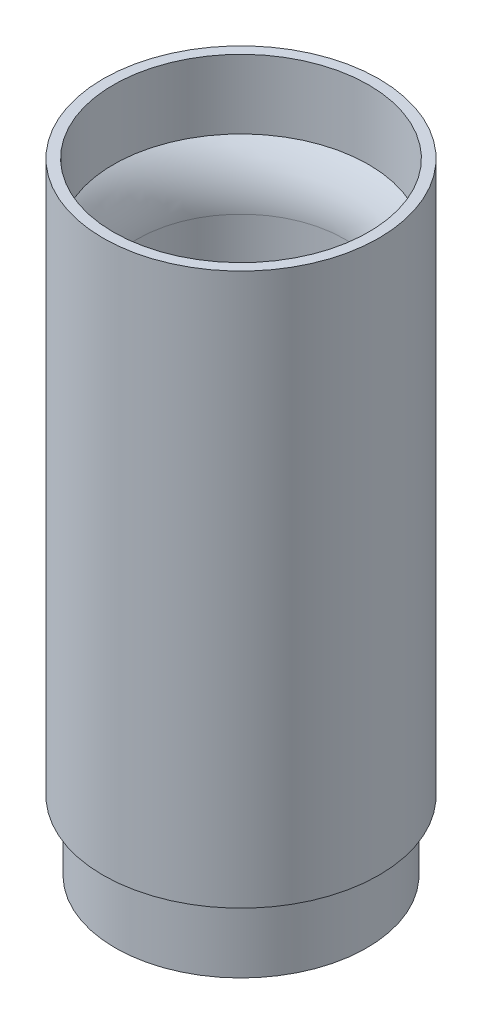
SolidWorks part; units mm, degrees
material "自定义塑料"
ref_plane "前视基准面" through (0, 0, 0) normal (0, 0, 1) x (1, 0, 0)
ref_plane "上视基准面" through (0, 0, 0) normal (0, 1, 0) x (1, 0, 0)
ref_plane "右视基准面" through (0, 0, 0) normal (1, 0, 0) x (0, 0, -1)
sketch "草图1" plane through (0, 0, 0) normal (0, 1, 0) x (1, 0, 0)
  circle A0 centre (0, 0) radius 18.25
  dimension "D1" = 36.5
extrude "凸台-拉伸1" add sketch "草图1" along normal blind 10
sketch "草图3" plane through (0, 0, 0) normal (0, -1, 0) x (1, 0, 0)
  circle A0 centre (0, 0) radius 15
extrude "切除-拉伸1" cut sketch "草图3" against normal blind 8
sketch "草图4" plane through (0, 10, 0) normal (0, 1, 0) x (1, 0, 0)
  circle A1 centre (0, 0) radius 20
  circle A2 centre (0, 0) radius 15
extrude "凸台-拉伸2" add sketch "草图4" along normal blind 70
sketch "草图5" plane through (0, 80, 0) normal (0, 1, 0) x (1, 0, 0)
  circle A0 centre (0, 0) radius 20
  circle A1 centre (0, 0) radius 18.5
extrude "凸台-拉伸3" add sketch "草图5" along normal blind 10
fillet "圆角1" radius 10 1 edges at (0, 80, 15)
